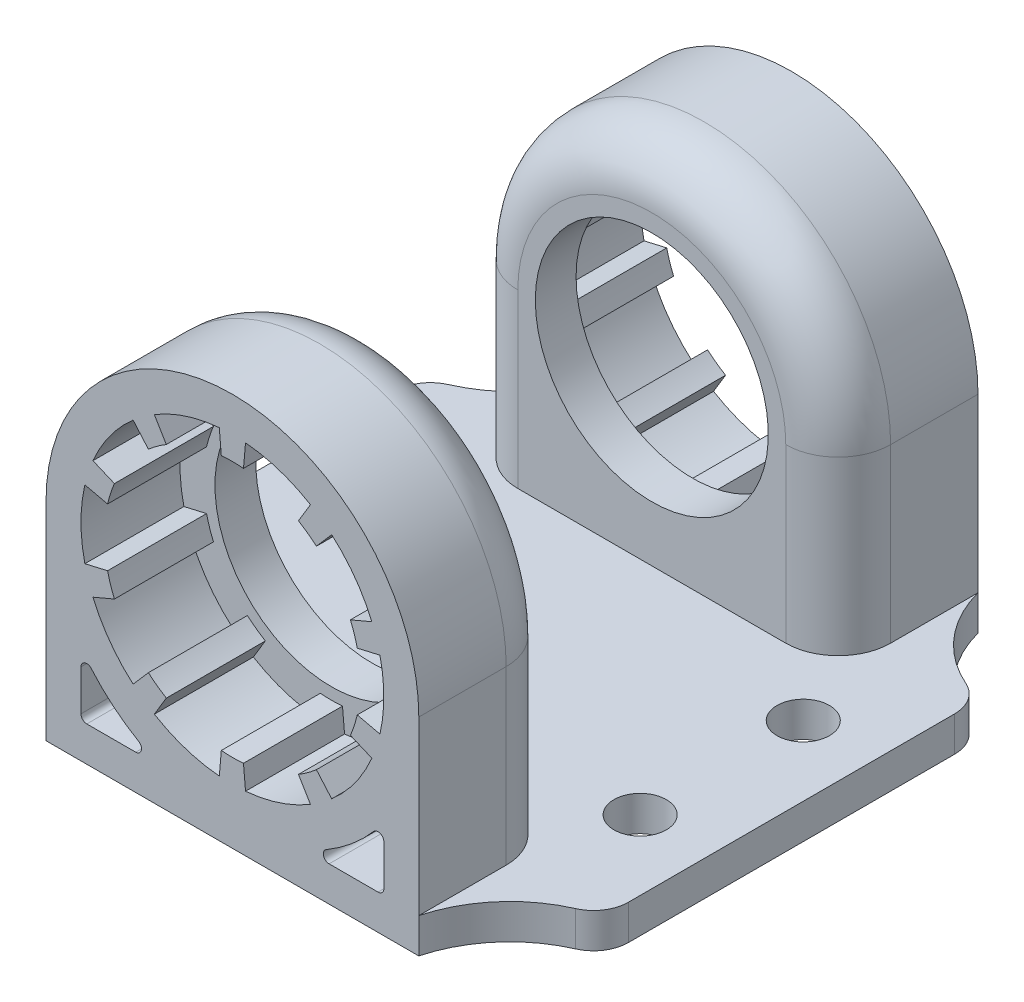
SolidWorks part; units mm, degrees
ref_plane "Alzado" through (0, 0, 0) normal (0, 0, 1) x (1, 0, 0)
ref_plane "Planta" through (0, 0, 0) normal (0, 1, 0) x (1, 0, 0)
ref_plane "Vista lateral" through (0, 0, 0) normal (1, 0, 0) x (0, 0, -1)
sketch "Croquis2" plane through (0, 0, 0) normal (0, 0, 1) x (1, 0, 0)
  line L1 (0, 0) -> (-32, 0)
  line L2 (0, 0) -> (0, 17.76)
  line L4 (-32, 0) -> (-32, 17.76)
  arc A0 (0, 17.76) -> (-32, 17.76) centre (-16, 17.76) ccw
  dimension "D1" = 32
  dimension "D2" = 17.76
extrude "Saliente-Extruir1" add sketch "Croquis2" along normal mid plane 12
sketch "Croquis3" plane through (0, 0, 6) normal (0, 0, 1) x (1, 0, 0)
  circle A0 centre (-16, 17.76) radius 4
  dimension "D1" = 8
extrude "Cortar-Extruir1" cut sketch "Croquis3" against normal through all
ref_plane "Plano1" through (-16, 0, 0) normal (-1, 0, 0) x (0, 0, 1)
sketch "Croquis4" plane through (0, 0, 6) normal (0, 0, 1) x (1, 0, 0)
  circle A0 centre (-16, 17.76) radius 13
  dimension "D1" = 26
extrude "Cortar-Extruir2" cut sketch "Croquis4" against normal blind 8.5
sketch "Croquis5" plane through (0, 0, -2.5) normal (0, 0, 1) x (1, 0, 0)
  circle A0 centre (-16, 17.76) radius 10
  dimension "D1" = 20
extrude "Cortar-Extruir3" cut sketch "Croquis5" against normal blind 8.5
ref_plane "Plano3" through (0, 0, -4) normal (0, 0, -1) x (-1, 0, 0)
sketch "Croquis6" plane through (0, 0, -6) normal (0, 0, -1) x (-1, 0, 0)
  line L0 (32, 17.76) -> (32, 0) construction
  line L1 (0, 0) -> (32, 0)
  line L2 (0, 0) -> (0, 3)
  line L3 (0, 3) -> (32, 3)
  line L4 (32, 0) -> (32, 3)
  dimension "D1" = 3
extrude "Saliente-Extruir2" add sketch "Croquis6" along normal blind 24
ref_plane "Plano2" through (0, 0, -18) normal (0, 0, -1) x (-1, 0, 0)
mirror "Simetría1" about plane through (0, 0, -18) normal (0, 0, -1) of "Cortar-Extruir3", "Cortar-Extruir2", "Saliente-Extruir1"
sketch "Croquis7" plane through (0, 0, 0) normal (0, 1, 0) x (1, 0, 0)
  line L0 (0, 42) -> (0, 30) construction
  line L1 (0, 35) -> (5, 35)
  line L2 (0, 35) -> (0, 1)
  line L3 (0, 1) -> (5, 1)
  line L4 (8, 32) -> (8, 4)
  line L5 (0, 42) -> (-32, 42) construction
  line L6 (-32, -6) -> (0, -6) construction
  line L7 (-16, 42) -> (-16, 38.616) construction
  line L8 (-32, 1) -> (-37, 1)
  line L9 (-40, 32) -> (-40, 4)
  line L10 (-32, 35) -> (-37, 35)
  line L11 (-32, 35) -> (-32, 1)
  arc A0 (5, 1) -> (8, 4) centre (5, 4) ccw
  arc A1 (5, 35) -> (8, 32) centre (5, 32) cw
  arc A2 (-37, 1) -> (-40, 4) centre (-37, 4) cw
  arc A3 (-37, 35) -> (-40, 32) centre (-37, 32) ccw
  dimension "D4" = 3
  dimension "D1" = 7
  dimension "D2" = 7
  dimension "D3" = 8
extrude "Saliente-Extruir3" add sketch "Croquis7" along normal blind 3
fillet "Redondeo1" radius 11 4 edges at (0, 1.5, -35) (0, 1.5, -1) (-32, 1.5, -1) (-32, 1.5, -35)
sketch "Croquis8" plane through (0, 3, 0) normal (0, 1, 0) x (1, 0, 0)
  line L0 (8, 4) -> (8, 32) construction
  line L2 (12.65, 18) -> (-12.65, 18) construction
  circle A0 centre (2, 25) radius 2.25
  circle A1 centre (2, 11) radius 2.25
  dimension "D1" = 4.5
  dimension "D2" = 6
  dimension "D3" = 7
extrude "Cortar-Extruir4" cut sketch "Croquis8" against normal through all
mirror "Simetría2" about plane through (-16, 0, 0) normal (-1, 0, 0) of "Cortar-Extruir4"
sketch "Croquis11" plane through (0, 0, 6) normal (0, 0, 1) x (1, 0, 0)
  line L0 (-17.125, 30.7112) -> (-16.9519, 28.7187)
  line L1 (-14.875, 30.7112) -> (-15.0481, 28.7187)
  line L2 (-16, 30.76) -> (-16, 28.76) construction
  circle A0 centre (-16, 17.76) radius 16 construction
  arc A2 (-15.0481, 28.7187) -> (-16.9519, 28.7187) centre (-16, 17.76) ccw
  circle A3 centre (-16, 17.76) radius 13 construction
  arc A4 (-14.875, 30.7112) -> (-17.125, 30.7112) centre (-16, 17.76) ccw
  dimension "D1" = 32
  dimension "D2" = 2.25
  dimension "D3" = 22
extrude "Saliente-Extruir4" add sketch "Croquis11" against normal up to surface (8.5 mm away) up to face at (-6, 17.76, -2.5)
pattern_circular "MatrizC1" count 10 over 360 about axis through (-16, 17.76, 6) along (0, 0, 1) of "Saliente-Extruir4"
mirror "Simetría3" about plane through (0, 0, -18) normal (0, 0, -1) of "MatrizC1", "Saliente-Extruir4"
fillet "Redondeo2" radius 4.5 6 edges at (0, 10.38, -6) (-32, 10.38, -6) (-16, 33.76, -6) (0, 10.38, -30) (-32, 10.38, -30) (-16, 33.76, -30)
sketch "Croquis12" plane through (0, 0, 6) normal (0, 0, 1) x (1, 0, 0)
  line L0 (-3, 3.5) -> (-3, 6.9897)
  line L1 (0, 3) -> (0, 17.76) construction
  line L2 (-3.5, 3) -> (-7.6993, 3)
  line L3 (-32, 0) -> (0, 0) construction
  arc A0 (-7.9508, 3.9321) -> (-3.8788, 7.316) centre (-16, 17.76) ccw
  arc A1 (-3, 3.5) -> (-3.5, 3) centre (-3.5, 3.5) cw
  arc A2 (-3, 6.9897) -> (-3.8788, 7.316) centre (-3.5, 6.9897) ccw
  arc A3 (-7.6993, 3) -> (-7.9508, 3.9321) centre (-7.6993, 3.5) cw
  dimension "D3" = 32
  dimension "D4" = 0.5
  dimension "D1" = 3
  dimension "D2" = 3
extrude "Cortar-Extruir5" cut sketch "Croquis12" against normal blind 9
mirror "Simetría4" about plane through (-16, 0, 0) normal (-1, 0, 0) of "Cortar-Extruir5"
mirror "Simetría5" about plane through (0, 0, -18) normal (0, 0, -1) of "Simetría4", "Cortar-Extruir5"
